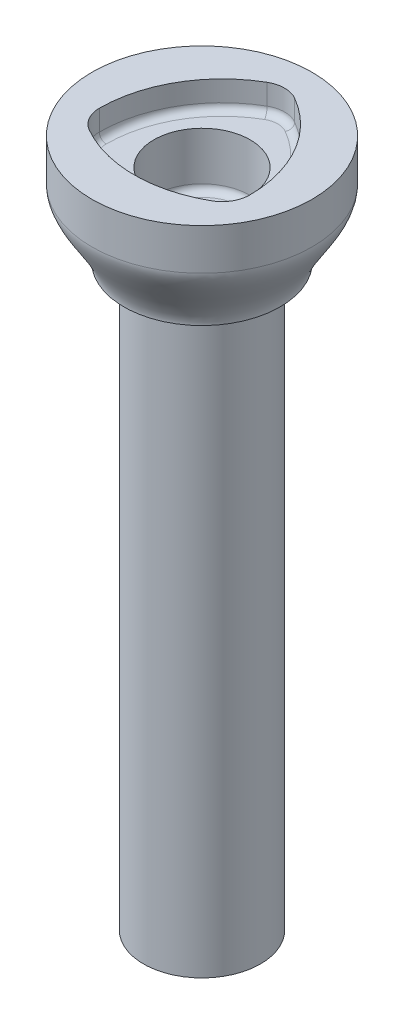
SolidWorks part; units mm, degrees
ref_plane "Front Plane" through (0, 0, 0) normal (0, 0, 1) x (1, 0, 0)
ref_plane "Top Plane" through (0, 0, 0) normal (0, 1, 0) x (1, 0, 0)
ref_plane "Right Plane" through (0, 0, 0) normal (1, 0, 0) x (0, 0, -1)
sketch "Sketch6" plane through (0, 0, 0) normal (0, 0, 1) x (1, 0, 0)
  line L0 (0, 0) -> (-8.5, 0)
  line L2 (0, 0) -> (0, 100)
  line L3 (0, 100) -> (-16, 100)
  line L4 (-16, 100) -> (-16, 94)
  line L5 (-16, 94) -> (-16, 91.39) construction
  line L6 (-16, 91.39) -> (-11.35, 86.74) construction
  line L7 (-11.35, 86.74) -> (-11.35, 84.13) construction
  line L8 (-11.35, 84.13) -> (-8.5, 84.13)
  line L9 (-8.5, 84.13) -> (-8.5, 0)
  spline S0 degree 3 poles (-16, 94) (-16, 91.39) (-11.35, 86.74) (-11.35, 84.13) knots 0 0 0 0 1 1 1 1
  point P9 (-10.05, 81.6044)
  dimension "D1" = 8.5
  dimension "D2" = 16
  dimension "D4" = 6
  dimension "D5" = 45
  dimension "D6" = 100
  dimension "D7" = 2.85
  dimension "D3" = 15.87
revolve "Revolve1" add sketch "Sketch6" angle 360 about L2
sketch "Sketch7" plane through (0, 100, 0) normal (0, 1, 0) x (1, 0, 0)
  line L1 (0, 8) -> (-6.9282, -4) construction
  line L2 (-6.9282, -4) -> (6.9282, -4) construction
  line L3 (6.9282, -4) -> (0, 8) construction
  circle A0 centre (0, 0) radius 8 construction
  arc A1 (-2, 11.4641) -> (2, 11.4641) centre (0, 8) cw
  arc A2 (10.9282, -4) -> (8.9282, -7.4641) centre (6.9282, -4) cw
  arc A3 (-8.9282, -7.4641) -> (-10.9282, -4) centre (-6.9282, -4) cw
  arc A4 (-10.9282, -4) -> (-2, 11.4641) centre (6.9282, -4) cw
  arc A5 (2, 11.4641) -> (10.9282, -4) centre (-6.9282, -4) cw
  arc A6 (8.9282, -7.4641) -> (-8.9282, -7.4641) centre (0, 8) cw
  circle A8 centre (0, 0) radius 12 construction
  dimension "D1" = 4
  dimension "D2" = 24
extrude "Cut-Extrude1" cut sketch "Sketch7" against normal blind 4
sketch "Sketch8" plane through (0, 96, 0) normal (0, 1, 0) x (1, 0, 0)
  circle A0 centre (0, 0) radius 7
  dimension "D1" = 14
extrude "Cut-Extrude2" cut sketch "Sketch8" against normal blind 8
fillet "Fillet1" radius 1 7 edges at (-10.3923, 96, 6) (-8.5359, 96, -4.9282) (0, 96, -12) (8.5359, 96, -4.9282) (10.3923, 96, 6) (0, 88, 7) (0, 96, 9.8564)
equation "\"Turbine_Cx\"= 23.74"
equation "\"Bearing_d\" = 17"
equation "\"Bearing_d1\"= 22.7"
equation "\"D7@Sketch6\" = ( \"Bearing_d1\" - \"Bearing_d\" ) / 2"
equation "\"D3@Sketch6\"=9 + ( (\"Turbine_Cx\" + 2 ) / 2 - 6 )"
